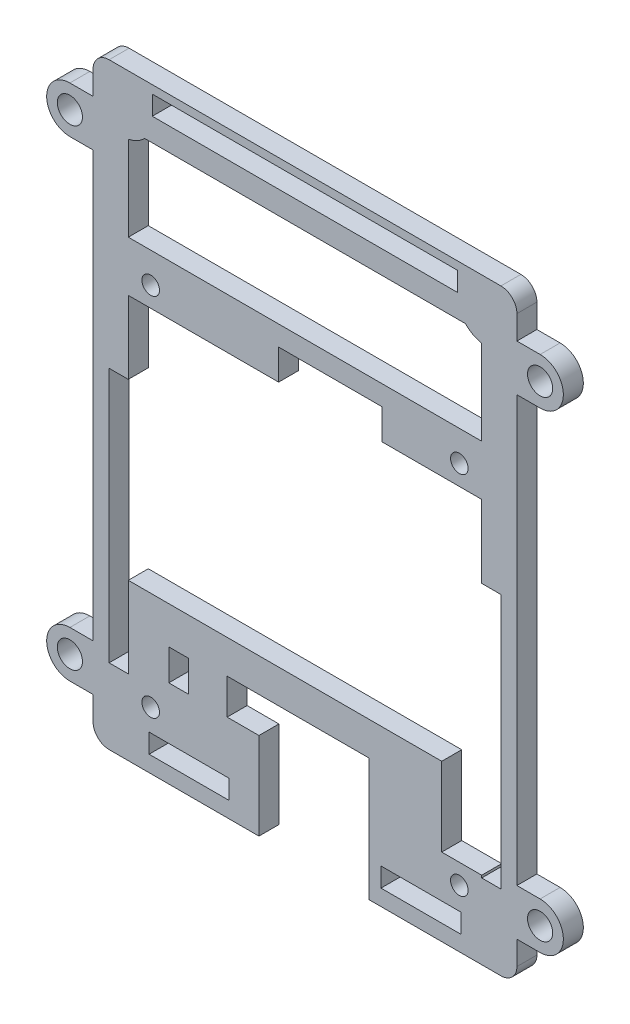
SolidWorks part; units mm, degrees
ref_plane "Front Plane" through (0, 0, 0) normal (0, 0, 1) x (1, 0, 0)
ref_plane "Top Plane" through (0, 0, 0) normal (0, 1, 0) x (1, 0, 0)
ref_plane "Right Plane" through (0, 0, 0) normal (1, 0, 0) x (0, 0, -1)
sketch "Sketch1" plane through (0, 0, 0) normal (0, 0, 1) x (1, 0, 0)
  line L0 (38.227, 0) -> (38.227, 13.8938)
  line L1 (52.832, 0) -> (40.132, 0) construction
  line L2 (38.227, 13.8938) -> (17.907, 13.8938)
  line L3 (17.907, 13.8938) -> (17.907, 8.255)
  line L4 (17.907, 8.255) -> (22.9616, 8.255)
  line L5 (22.9616, 8.255) -> (22.9616, 0)
  line L6 (40.132, 0) -> (16.002, 0) construction
  line L8 (0, 19.2278) -> (49.784, 19.2278)
  line L9 (49.784, 19.2278) -> (49.784, 6.731)
  line L10 (49.784, 6.731) -> (56.134, 6.731)
  line L11 (52.578, 6.731) -> (56.134, 6.731) construction
  line L12 (16.002, 0) -> (3.302, 0) construction
  line L13 (6.4262, 13.2842) -> (9.6012, 13.2842)
  line L14 (6.4262, 13.2842) -> (6.4262, 8.3312)
  line L15 (6.4262, 8.3312) -> (9.6012, 8.3312)
  line L16 (9.6012, 13.2842) -> (9.6012, 8.3312)
  line L17 (0, 6.35) -> (0, -3.048) construction
  line L18 (0, 6.35) -> (0, 46.863) construction
  line L19 (16.002, -3.048) -> (16.002, 0) construction
  line L20 (16.002, -3.048) -> (3.302, -3.048) construction
  line L21 (3.302, -3.048) -> (3.302, 0) construction
  line L22 (40.132, -3.048) -> (40.132, 0) construction
  line L23 (52.832, -3.048) -> (40.132, -3.048) construction
  line L24 (52.832, -3.048) -> (52.832, 0) construction
  line L25 (59.182, 6.35) -> (56.134, 6.35) construction
  line L28 (59.182, 46.863) -> (56.134, 46.863) construction
  line L29 (-3.048, 46.863) -> (0, 46.863) construction
  line L30 (-3.048, 6.35) -> (-3.048, 46.863) construction
  line L31 (-3.048, 6.35) -> (0, 6.35) construction
  line L32 (16.002, -3.048) -> (16.002, 0)
  line L33 (16.002, -3.048) -> (3.302, -3.048)
  line L34 (3.302, -3.048) -> (3.302, 0)
  line L35 (16.002, 0) -> (3.302, 0)
  line L36 (40.132, -3.048) -> (40.132, 0)
  line L37 (52.832, -3.048) -> (40.132, -3.048)
  line L38 (52.832, 0) -> (40.132, 0)
  line L39 (52.832, -3.048) -> (52.832, 0)
  line L40 (59.182, 6.35) -> (56.134, 6.35)
  line L41 (59.182, 46.863) -> (59.182, 6.35)
  line L42 (56.134, 46.863) -> (56.134, 6.35)
  line L43 (59.182, 46.863) -> (56.134, 46.863)
  line L44 (-3.048, 46.863) -> (0, 46.863)
  line L45 (0, 6.35) -> (0, 46.863)
  line L46 (-3.048, 6.35) -> (-3.048, 46.863)
  line L47 (-3.048, 6.35) -> (0, 6.35)
  line L48 (59.182, -5.588) -> (-3.048, -5.588) construction
  line L49 (59.182, -5.588) -> (-3.048, -5.588)
  line L50 (-5.588, -3.048) -> (-5.588, 86.7664)
  line L51 (61.722, -3.048) -> (61.722, 86.7664)
  line L52 (0, 66.421) -> (56.134, 66.421)
  line L53 (3.556, 58.42) -> (0, 58.42) construction
  line L54 (52.578, 58.42) -> (56.134, 58.42) construction
  line L55 (3.556, 58.42) -> (0, 58.42)
  line L56 (52.578, 58.42) -> (56.134, 58.42)
  line L57 (3.556, 58.42) -> (23.876, 58.42)
  line L58 (23.876, 58.42) -> (23.876, 63.246)
  line L59 (23.876, 63.246) -> (40.259, 63.246)
  line L60 (40.259, 63.246) -> (40.259, 58.42)
  line L61 (40.259, 58.42) -> (52.578, 58.42)
  line L63 (-3.048, 89.3064) -> (59.182, 89.3064)
  line L64 (0, 83.2104) -> (56.134, 83.2104)
  line L67 (0, 46.863) -> (0, 83.2104)
  line L68 (56.134, 83.2104) -> (56.134, 46.863)
  line L69 (0, 83.2104) -> (0, 46.863)
  line L70 (3.81, 86.7664) -> (52.324, 86.7664)
  line L71 (3.81, 86.7664) -> (3.81, 84.963)
  line L72 (3.81, 84.963) -> (52.324, 84.963)
  line L73 (52.324, 86.7664) -> (52.324, 84.963)
  line L74 (56.134, 83.2104) -> (56.134, 46.863)
  line L76 (38.227, 0) -> (38.227, -5.588)
  line L77 (22.9616, 0) -> (22.9616, -5.588)
  circle A0 centre (3.556, 3.556) radius 1.397 construction
  circle A1 centre (52.578, 3.556) radius 1.397 construction
  circle A2 centre (3.556, 61.595) radius 1.397 construction
  circle A3 centre (52.578, 61.595) radius 1.397 construction
  circle A4 centre (3.556, 3.556) radius 1.397
  circle A5 centre (52.578, 3.556) radius 1.397
  circle A6 centre (3.556, 61.595) radius 1.397
  circle A7 centre (52.578, 61.595) radius 1.397
  arc A8 (-5.588, -3.048) -> (-3.048, -5.588) centre (-3.048, -3.048) ccw construction
  arc A9 (59.182, -5.588) -> (61.722, -3.048) centre (59.182, -3.048) ccw construction
  arc A10 (-5.588, -3.048) -> (-3.048, -5.588) centre (-3.048, -3.048) ccw
  arc A11 (59.182, -5.588) -> (61.722, -3.048) centre (59.182, -3.048) ccw
  arc A12 (59.182, 89.3064) -> (61.722, 86.7664) centre (59.182, 86.7664) cw
  arc A13 (-5.588, 86.7664) -> (-3.048, 89.3064) centre (-3.048, 86.7664) cw
  point P74 (-5.588, 89.3064)
  dimension "D12" = 3.429
  dimension "D17" = 2.54
  dimension "D1" = 20.32
  dimension "D3" = 15.2654
  dimension "D4" = 8.255
  dimension "D5" = 19.4818
  dimension "D6" = 5.334
  dimension "D7" = 3.175
  dimension "D8" = 4.953
  dimension "D9" = 8.3312
  dimension "D10" = 6.4262
  dimension "D11" = 6.35
  dimension "D13" = 23.495
  dimension "D14" = 23.876
  dimension "D15" = 3.175
  dimension "D16" = 1.8034
  dimension "D18" = 3.556
  dimension "D19" = 3.81
  dimension "D20" = 3.81
  dimension "D21" = 15.875
  dimension "D22" = 16.7894
extrude "Boss-Extrude1" add sketch "Sketch1" along normal blind 3.175 contours L60 L61 L56 L52 L45 L55 L57 L58 L59 A7 A6 | A13 L50 A10 L49 A11 L51 A12 L63 A5 A4 L70 L73 L72 L71 L13 L16 L15 L14 L35 L32 L33 L34 L39 L37 L36 L38 L40 L10 L9 L8 L45 L47 region at (39.3904, 6.9469, 0) region at (0.567, 62.4205, 0)
sketch "Sketch2" plane through (0, 0, 3.175) normal (0, 0, 1) x (1, 0, 0)
  line L0 (-5.588, -3.048) -> (-5.588, 86.7664) construction
  line L1 (-3.048, 89.3064) -> (59.182, 89.3064) construction
  line L2 (61.722, -3.048) -> (61.722, 86.7664) construction
  line L3 (0, 81.3054) -> (56.134, 81.3054)
  line L4 (0, 66.421) -> (0, 83.2104) construction
  line L5 (56.134, 83.2104) -> (56.134, 66.421) construction
  line L6 (0, 79.9092) -> (0, 83.2104)
  line L7 (0, 83.2104) -> (56.134, 83.2104)
  line L8 (56.134, 83.2104) -> (56.134, 79.9092)
  circle A0 centre (-0.8509, 84.5693) radius 4.7371
  circle A1 centre (56.9849, 84.5693) radius 4.7371
  dimension "D1" = 9.4742
  dimension "D2" = 8.001
extrude "Boss-Extrude2" add sketch "Sketch2" against normal up to vertex (3.175 mm away) contours L3 A0 L7 L6 | L6 A0 L3 | A1 L7 A0 L3 | L7 A1 L3 L8 | L3 A1 L8 region at (1.6331, 82.3113, 3.175) region at (0.9571, 80.7762, 3.175) region at (28.067, 82.2509, 3.175) region at (54.5009, 82.3113, 3.175) region at (55.1769, 80.7762, 3.175) up to point (0, 83.2104, 0)
sketch "Sketch3" plane through (0, 0, 3.175) normal (0, 0, 1) x (1, 0, 0)
  line L0 (20.7518, 8.255) -> (20.7518, -5.588)
  line L3 (17.907, 8.255) -> (22.9616, 8.255) construction
  line L4 (22.9616, -5.588) -> (-3.048, -5.588) construction
  line L5 (17.907, 13.8938) -> (15.6972, 13.8938)
  line L6 (15.6972, 13.8938) -> (15.6972, 8.255)
  line L7 (15.6972, 8.255) -> (17.907, 8.255)
  line L8 (17.907, 13.8938) -> (17.907, 8.255)
  line L9 (20.7518, 8.255) -> (22.9616, 8.255)
  line L10 (22.9616, 8.255) -> (22.9616, -5.588)
  line L11 (22.9616, -5.588) -> (20.7518, -5.588)
  dimension "D1" = 2.2098
  dimension "D2" = 2.2098
extrude "Cut-Extrude1" cut sketch "Sketch3" against normal through all
sketch "Sketch4" plane through (0, 0, 3.175) normal (0, 0, 1) x (1, 0, 0)
  line B0 (6.4923, 13.2132) -> (9.6673, 13.2132)
  line B1 (6.4923, 13.2132) -> (6.4923, 8.2602)
  line B2 (9.6673, 13.2132) -> (9.6673, 8.2602)
  line B3 (6.4923, 8.2602) -> (9.6673, 8.2602)
  line B4 (15.7369, 13.9566) -> (15.7369, 8.184)
  line B5 (15.7369, 8.184) -> (20.781, 8.184)
  line B6 (38.329, 13.9566) -> (15.7369, 13.9566)
  line B7 (38.329, -5.5096) -> (38.329, 13.9566)
  line B8 (20.781, 8.184) -> (20.781, -5.5096)
  circle B9 centre (3.6221, 3.485) radius 1.397
  circle B10 centre (52.6441, 3.485) radius 1.397
sketch_block_instance "Block2-1"
sketch_block "Block2"
sketch "Sketch6" plane through (0, 0, 3.175) normal (0, 0, 1) x (1, 0, 0)
  line L1 (3.81, 84.963) -> (52.324, 84.963)
  line L2 (3.81, 84.963) -> (3.81, 88.011)
  line L3 (3.81, 88.011) -> (52.324, 88.011)
  line L4 (52.324, 84.963) -> (52.324, 88.011)
extrude "Cut-Extrude2" cut sketch "Sketch6" against normal through all
sketch "Sketch7" plane through (0, 0, 3.175) normal (0, 0, 1) x (1, 0, 0)
  line L1 (3.81, 84.963) -> (52.324, 84.963)
  line L2 (3.81, 84.963) -> (3.81, 88.011)
  line L3 (3.81, 88.011) -> (52.324, 88.011)
  line L4 (52.324, 84.963) -> (52.324, 88.011)
  dimension "D1" = 3.048
sketch "Sketch5" plane through (0, 0, 3.175) normal (0, 0, 1) x (1, 0, 0)
  line L0 (-9.2771, 4.4135) -> (65.4111, 4.4135) construction
  line L1 (65.4111, 4.4135) -> (65.4111, 79.3049) construction
  line L2 (65.4111, 79.3049) -> (-9.2771, 79.3049) construction
  line L3 (-9.2771, 79.3049) -> (-9.2771, 4.4135) construction
  line L4 (-9.2771, 41.8592) -> (-5.588, 41.8592) construction
  line L5 (-5.588, -3.048) -> (-5.588, 86.7664) construction
  line L6 (61.722, 41.8592) -> (65.4111, 41.8592) construction
  line L7 (61.722, -3.048) -> (61.722, 86.7664) construction
  line L8 (-9.2771, 82.994) -> (-5.588, 82.994)
  line L9 (-9.2771, 75.6158) -> (-5.588, 75.6158)
  line L10 (-9.2771, 8.1026) -> (-5.588, 8.1026)
  line L11 (-9.2771, 0.7244) -> (-5.588, 0.7244)
  line L12 (65.4111, 0.7244) -> (61.722, 0.7244)
  line L13 (65.4111, 75.6158) -> (61.722, 75.6158)
  line L14 (65.4111, 8.1026) -> (61.722, 8.1026)
  line L15 (65.4111, 82.994) -> (61.722, 82.994)
  line L16 (-5.588, 82.994) -> (-5.588, 75.6158)
  line L17 (61.722, 82.994) -> (61.722, 75.6158)
  line L19 (61.722, 0.7244) -> (61.722, 8.1026)
  line L20 (-5.588, 8.1026) -> (-5.588, 0.7244)
  circle A0 centre (65.4111, 79.3049) radius 2
  circle A1 centre (65.4111, 4.4135) radius 2
  circle A2 centre (-9.2771, 4.4135) radius 2
  circle A3 centre (-9.2771, 79.3049) radius 2
  circle A4 centre (-9.2771, 4.4135) radius 3.6891
  circle A5 centre (-9.2771, 79.3049) radius 3.6891
  circle A6 centre (65.4111, 79.3049) radius 3.6891
  circle A7 centre (65.4111, 4.4135) radius 3.6891
  dimension "D1" = 70.6882
  dimension "D2" = 70.8914
  dimension "D3" = 4
extrude "Boss-Extrude3" add sketch "Sketch5" against normal up to vertex (3.175 mm away) contours A4 L20 L10 | A4 L11 L20 | A4 A2 | A7 A1 | A7 L19 L12 | A7 L14 L19 | A6 A0 | A6 L17 L13 | A6 L15 L17 | A5 L9 L16 | A5 A3 | A5 L16 L8 region at (-6.412, 82.17, 3.175) region at (-6.7423, 81.8397, 3.175) region at (-6.412, 76.4398, 3.175) region at (-6.412, 7.2786, 3.175) region at (-6.7423, 6.9483, 3.175) region at (-6.412, 1.5484, 3.175) region at (62.8763, 1.8787, 3.175) region at (62.546, 1.5484, 3.175) region at (62.546, 7.2786, 3.175) region at (62.8763, 76.7701, 3.175) region at (62.546, 76.4398, 3.175) region at (62.546, 82.17, 3.175) up to point (-5.588, 86.7664, 0)
